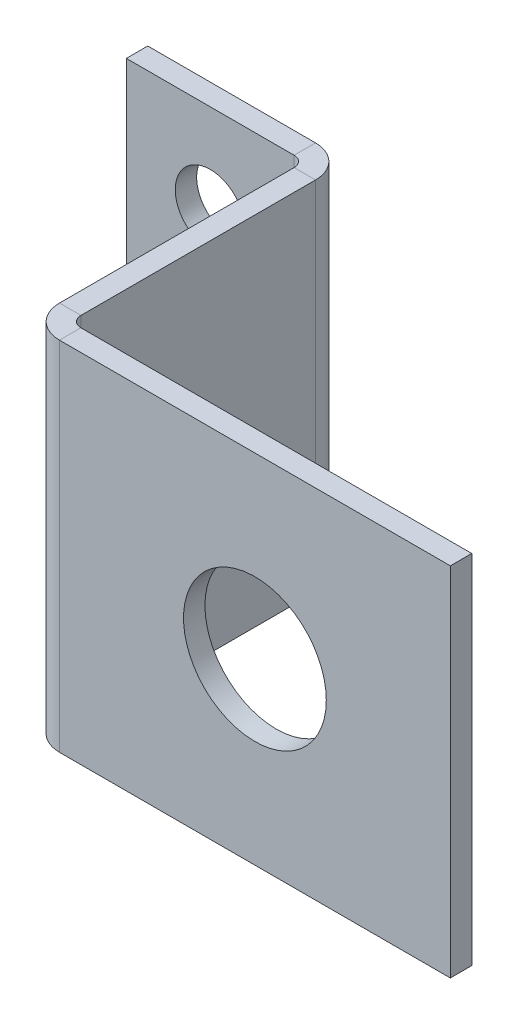
SolidWorks part; units mm, degrees
note: The reader was unsure of these and kept them because the rebuilt part matched: flange length of "Edge-Flange1", "Edge-Flange2".
material "6061-T6 (SS)"
ref_plane "Front Plane" through (0, 0, 0) normal (0, 0, 1) x (1, 0, 0)
ref_plane "Top Plane" through (0, 0, 0) normal (0, 1, 0) x (1, 0, 0)
ref_plane "Right Plane" through (0, 0, 0) normal (1, 0, 0) x (0, 0, -1)
sketch "Sketch5" plane through (0, 0, 0) normal (0, 0, 1) x (1, 0, 0)
  line L1 (0, 0) -> (12.7, 0)
  line L2 (0, 0) -> (0, 25.4)
  line L3 (0, 25.4) -> (12.7, 25.4)
  line L4 (12.7, 0) -> (12.7, 25.4)
  dimension "D1" = 12.7
  dimension "D2" = 25.4
base flange "Base-Flange1" sketch "Sketch5" thickness 1.524 reverse thickness direction no parameters "D1"=10
edge flange "Edge-Flange1" sketch "Sketch12" flange angle 90 flange length 19.7444 flange position material outside bend radius 0.762 thickness 1.524 relief rectangular parameters "D6"=10
sketch "Sketch12" plane through (12.7, 0, 0) normal (1, 0, 0) x (0, 1, 0)
  line L0 (0, 0) -> (25.4, 0) construction
  line L1 (0, 0) -> (25.4, 0)
  line L2 (0, 0) -> (0, 18.2204)
  line L3 (0, 18.2204) -> (25.4, 18.2204)
  line L4 (25.4, 18.2204) -> (25.4, 0)
  line L5 (0, -1.524) -> (25.4, -1.524) construction
  dimension "D1" = 19.7444
bend "EdgeBend1" bend radius 0.762 bend angle 90 parameters "D5"=1
edge flange "Edge-Flange2" sketch "Sketch15" flange angle 90 flange length 30.099 flange position material outside bend radius 0.762 thickness 1.524 relief rectangular parameters "D6"=10
sketch "Sketch15" plane through (14.224, 0, 18.2204) normal (0, 0, 1) x (0, -1, 0)
  line L2 (-25.4, 0) -> (-25.4, 28.575)
  line L3 (-25.4, 28.575) -> (0, 28.575)
  line L4 (0, 28.575) -> (0, 0)
  line L5 (-25.4, 0) -> (0, 0) construction
  line L6 (-25.4, 0) -> (0, 0)
  dimension "D1" = 28.575
bend "EdgeBend2" bend radius 0.762 bend angle 90 parameters "D5"=2
sketch "Sketch16" plane through (0, 0, 19.7444) normal (0, 0, 1) x (1, 0, 0)
  line L0 (28.8925, 25.4) -> (28.8925, 12.7) construction
  line L1 (42.799, 25.4) -> (14.986, 25.4) construction
  line L2 (28.8925, 12.7) -> (28.8925, 0) construction
  line L3 (14.986, 0) -> (42.799, 0) construction
  circle A0 centre (28.8925, 12.7) radius 5.08
  dimension "D1" = 10.16
extrude "Cut-Extrude1" cut sketch "Sketch16" against normal up to next normal cut yes
hole_wizard "#10 Clearance Hole2" positions "Sketch17" profile "Sketch18" hole size "#10" standard "ANSI Inch" end condition through all
sketch "Sketch17" plane through (0, 0, 0) normal (0, 0, 1) x (1, 0, 0)
  line L0 (5.969, 25.4) -> (5.969, 19.05) construction
  line L1 (11.938, 25.4) -> (0, 25.4) construction
  line L2 (5.969, 19.05) -> (5.969, 6.35) construction
  line L3 (5.969, 6.35) -> (5.969, 0) construction
  line L4 (0, 0) -> (11.938, 0) construction
  point P0 (5.969, 19.05)
  point P2 (5.969, 6.35)
  dimension "D1" = 12.7
sketch "Sketch18" plane through (5.969, 19.05, 0) normal (1, 0, 0) x (0, -1, 0)
  line L0 (0, 0) -> (0, 1.524)
  line L1 (0, 1.524) -> (2.4892, 1.524)
  line L2 (2.4892, 1.524) -> (2.4892, 0)
  line L5 (2.4892, 0) -> (0, 0)
  line L11 (0, -6.35) -> (0, 107.95) construction
  dimension "Thru Hole Dia." = 4.9784
  dimension "Thru Hole Depth" = 1.524
sketch "Bend-Lines1" [suppressed] plane through (0, 0, 0) normal (0, 1, 0) x (1, 0, 0)
sketch "Bounding-Box1" [suppressed] plane through (0, 0, 0) normal (0, 1, 0) x (1, 0, 0)
sheet metal parameters "Sheet-Metal3" thickness 1.524 parameters "D1"=10
flat pattern "Flat-Pattern3" [suppressed]
sketch "Bend-Lines2" plane through (0, 0, 0) normal (0, 1, 0) x (1, 0, 0)
sketch3d "Bounding-Box2" [suppressed]
  line L0 (-25.4, 31.75, 0) -> (-25.4, 0, 0) construction
  line L1 (0, 31.75, 0) -> (0, 0, 0) construction
  line L2 (-25.4, 31.75, 0) -> (0, 31.75, 0) construction
  line L3 (-25.4, 0, 0) -> (0, 0, 0) construction
sheet metal parameters "Sheet-Metal4" thickness 1.524 parameters "D1"=10
flat pattern "Flat-Pattern3"
sketch "Bend-Lines2" plane through (0, 0, 0) normal (0, 0, 1) x (1, 0, 0)
  line L0 (19.4849, 0) -> (19.4849, 25.4) construction
  line L1 (19.4849, 0) -> (19.4849, 25.4) construction
sketch3d "Bounding-Box2" [suppressed]
  line L0 (0, 0, 0) -> (39.6643, 0, 0) construction
  line L1 (0, 25.4, 0) -> (39.6643, 25.4, 0) construction
  line L2 (0, 0, 0) -> (0, 25.4, 0) construction
  line L3 (39.6643, 0, 0) -> (39.6643, 25.4, 0) construction
bend of the flat pattern "Flatten-<EdgeBend1>1"
sheet metal parameters "Sheet-Metal5" thickness 1.524 parameters "D1"=10
flat pattern "Flat-Pattern3"
sketch "Bend-Lines2" plane through (0, 0, 0) normal (0, 0, 1) x (1, 0, 0)
  line L0 (19.4849, 0) -> (19.4849, 25.4) construction
  line L1 (19.4849, 0) -> (19.4849, 25.4) construction
  line L2 (40.0993, 0) -> (40.0993, 25.4) construction
  line L3 (40.0993, 0) -> (40.0993, 25.4) construction
sketch3d "Bounding-Box2" [suppressed]
  line L0 (0, 0, 0) -> (63.0132, 0, 0) construction
  line L1 (0, 25.4, 0) -> (63.0132, 25.4, 0) construction
  line L2 (0, 0, 0) -> (0, 25.4, 0) construction
  line L3 (63.0132, 0, 0) -> (63.0132, 25.4, 0) construction
bend of the flat pattern "Flatten-<EdgeBend1>1"
bend of the flat pattern "Flatten-<EdgeBend2>1"
sheet metal parameters "Sheet-Metal6" thickness 1.524 parameters "D1"=10
flat pattern "Flat-Pattern3"
sketch "Bend-Lines2" plane through (0, 0, 0) normal (0, 0, 1) x (1, 0, 0)
  line L0 (13.1349, 0) -> (13.1349, 25.4) construction
  line L1 (13.1349, 0) -> (13.1349, 25.4) construction
  line L2 (31.4633, 0) -> (31.4633, 25.4) construction
  line L3 (31.4633, 0) -> (31.4633, 25.4) construction
sketch3d "Bounding-Box2" [suppressed]
  line L0 (0, 0, 0) -> (60.4732, 0, 0) construction
  line L1 (0, 25.4, 0) -> (60.4732, 25.4, 0) construction
  line L2 (0, 0, 0) -> (0, 25.4, 0) construction
  line L3 (60.4732, 0, 0) -> (60.4732, 25.4, 0) construction
bend of the flat pattern "Flatten-<EdgeBend1>1"
bend of the flat pattern "Flatten-<EdgeBend2>1"
sheet metal parameters "Sheet-Metal7" thickness 1.524 parameters "D1"=10
flat pattern "Flat-Pattern3"
sketch "Bend-Lines2" plane through (0, 0, 0) normal (0, 0, 1) x (1, 0, 0)
  line L0 (13.1349, 0) -> (13.1349, 25.4) construction
  line L1 (13.1349, 0) -> (13.1349, 25.4) construction
  line L2 (32.2253, 0) -> (32.2253, 25.4) construction
  line L3 (32.2253, 0) -> (32.2253, 25.4) construction
sketch3d "Bounding-Box2" [suppressed]
  line L0 (0, 0, 0) -> (61.2352, 0, 0) construction
  line L1 (0, 25.4, 0) -> (61.2352, 25.4, 0) construction
  line L2 (0, 0, 0) -> (0, 25.4, 0) construction
  line L3 (61.2352, 0, 0) -> (61.2352, 25.4, 0) construction
bend of the flat pattern "Flatten-<EdgeBend1>1"
bend of the flat pattern "Flatten-<EdgeBend2>1"
